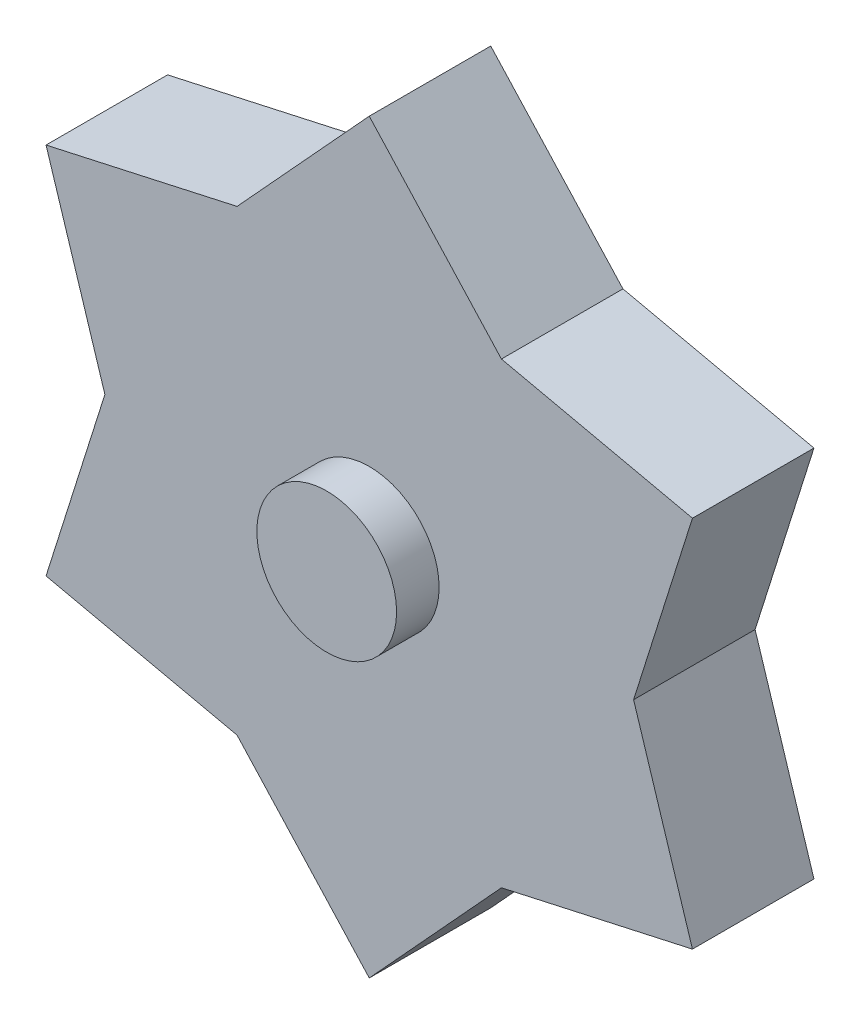
SolidWorks part; units mm, degrees
ref_plane "Front Plane" through (0, 0, 0) normal (0, 0, 1) x (1, 0, 0)
ref_plane "Top Plane" through (0, 0, 0) normal (0, 1, 0) x (1, 0, 0)
ref_plane "Right Plane" through (0, 0, 0) normal (1, 0, 0) x (0, 0, -1)
sketch "Sketch1" plane through (0, 0, 0) normal (0, 0, 1) x (1, 0, 0)
  line L0 (0, 6.1428) -> (0, -5.749) construction
  line L1 (-3.0597, 2.8037) -> (0, 6.1428)
  line L2 (0, 6.1428) -> (3.0597, 2.8037)
  line L3 (0.8982, 4.0516) -> (5.3198, 3.0714)
  line L4 (5.3198, 3.0714) -> (3.9579, -1.2479)
  line L5 (3.9579, 1.2479) -> (5.3198, -3.0714)
  line L6 (5.3198, -3.0714) -> (0.8982, -4.0516)
  line L7 (3.0597, -2.8037) -> (0, -6.1428)
  line L8 (0, -6.1428) -> (-3.0597, -2.8037)
  line L9 (-0.8982, -4.0516) -> (-5.3198, -3.0714)
  line L10 (-5.3198, -3.0714) -> (-3.9579, 1.2479)
  line L11 (-3.9579, -1.2479) -> (-5.3198, 3.0714)
  line L12 (-5.3198, 3.0714) -> (-0.8982, 4.0516)
  circle A0 centre (0, 0) radius 1.15
  circle A1 centre (0, 0) radius 4.15
  point P26 (0, 0)
  dimension "D1" = 2.3
  dimension "D3" = 85
  dimension "D4" = 42.5
  dimension "D2" = 3
  dimension "D5" = 6
extrude "Boss-Extrude1" add sketch "Sketch1" against normal blind 2 contours A1 A0 | A1 L1 L12 L11 L10 | L2 L0 A1 L3 | L0 L1 L12 A1 | A1 L12 L1 | A1 L2 L3 | A1 L5 L4 L3 L2 | L0 A1 A0 | A1 L11 L10 L9 L8 | A1 L10 L11 | A1 L8 L9 | A1 L9 L8 L7 L6 | A1 L6 L7 | A1 L7 L6 L5 L4 | A1 L4 L5 | A0 region at (0.718, 4.7126, 0) region at (-0.718, 4.7126, 0) region at (1.8672, 0, 0) region at (-1.8672, 0, 0) region at (-2.0957, 3.6299, 0) region at (-4.0813, 2.3563, 0) region at (4.0813, 2.3563, 0) region at (2.0957, 3.6299, 0) region at (-4.1915, 0, 0) region at (-4.0813, -2.3563, 0) region at (4.1915, 0, 0) region at (4.0813, -2.3563, 0) region at (0.4572, -4.1746, 0) region at (-2.0957, -3.6299, 0) region at (2.0957, -3.6299, 0)
extrude "Boss-Extrude2" add sketch "Sketch1<4>" along normal blind 0.7 contours A0 L0 | L0 A0 region at (0.4881, 0, 0) region at (-0.4881, 0, 0)
sketch "Sketch1<4>" plane through (0, 0, 0) normal (0, 0, 1) x (1, 0, 0) same geometry as "Sketch1"
